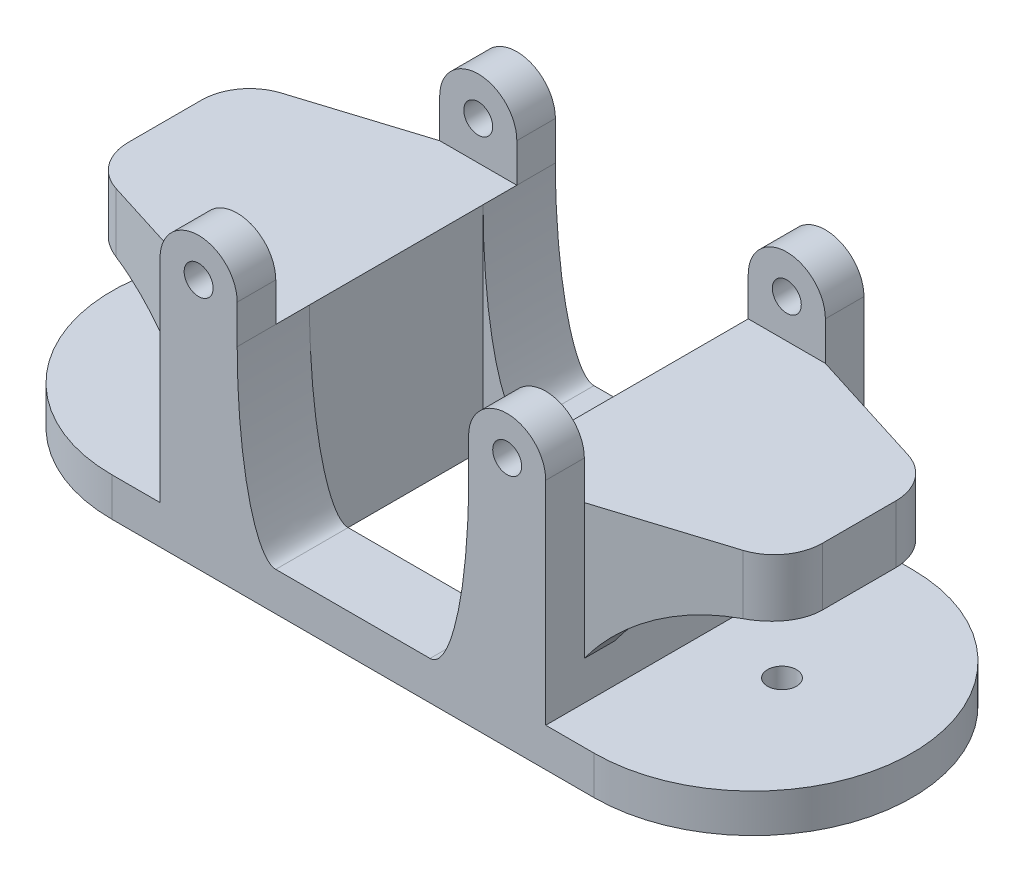
SolidWorks part; units mm, degrees
ref_plane "Front Plane" through (0, 0, 0) normal (0, 0, 1) x (1, 0, 0)
ref_plane "Top Plane" through (0, 0, 0) normal (0, 1, 0) x (1, 0, 0)
ref_plane "Right Plane" through (0, 0, 0) normal (1, 0, 0) x (0, 0, -1)
sketch "Sketch1" plane through (0, 0, 0) normal (0, 1, 0) x (1, 0, 0)
  line L1 (-16, 16.5) -> (16, 16.5)
  line L2 (-16, 16.5) -> (-16, -16.5)
  line L3 (-16, -16.5) -> (16, -16.5)
  line L4 (16, 16.5) -> (16, -16.5)
  line L5 (-16, 16.5) -> (16, -16.5) construction
  line L6 (-16, -16.5) -> (16, 16.5) construction
  point P0 (0, 0)
  dimension "D1" = 33
  dimension "D2" = 32
extrude "Boss-Extrude1" add sketch "Sketch1" along normal blind 18 contours L4 L3 L2 L1
shell "Shell1" thickness 4 removed face at (0, 18, 0)
sketch "Sketch2" plane through (0, 0, 0) normal (0, 0, 1) x (1, 0, 0)
  line L8 (-16, 0) -> (-20, 0)
  line L17 (-20, 0) -> (-20, 22)
  line L19 (-12, 22) -> (-12, 18)
  line L20 (-16, 18) -> (16, 18) construction
  line L21 (-12, 18) -> (-16, 18)
  line L22 (-16, 18) -> (-16, 0)
  line L23 (0, -9.9) -> (0, 9.9) construction
  line L24 (16, 18) -> (16, 0)
  line L25 (12, 18) -> (16, 18)
  line L26 (12, 22) -> (12, 18)
  line L27 (20, 0) -> (20, 22)
  line L28 (16, 0) -> (20, 0)
  arc A2 (-20, 22) -> (-12, 22) centre (-16, 22) cw
  circle A3 centre (-16, 22) radius 1.5
  circle A4 centre (16, 22) radius 1.5
  arc A5 (20, 22) -> (12, 22) centre (16, 22) ccw
  dimension "D2" = 4
  dimension "D3" = 3
  dimension "D1" = 4
extrude "Boss-Extrude2" add sketch "Sketch2" along normal mid plane 33
sketch "Sketch10" plane through (-12, 0, 0) normal (1, 0, 0) x (0, 0, -1)
  line L1 (-12.5, 26) -> (12.5, 26)
  line L2 (-12.5, 26) -> (-12.5, 18)
  line L3 (-12.5, 18) -> (12.5, 18)
  line L4 (12.5, 26) -> (12.5, 18)
  line L5 (16.5, 26) -> (-16.5, 26) construction
  line L6 (-16.5, 0) -> (16.5, 0) construction
  point P4 (0, 18)
  dimension "D1" = 25
  dimension "D2" = 18
extrude "Cut-Extrude5" cut sketch "Sketch10" against normal up to next and the other way up to next
sketch "Sketch11" plane through (0, 18, 0) normal (0, 1, 0) x (1, 0, 0)
  line L0 (-20, 12.5) -> (-32.5, 8.5689)
  line L1 (-36, 3.7992) -> (-36, -3.7992)
  line L2 (-32.5, -8.5689) -> (-20, -12.5)
  line L3 (-12, -12.5) -> (-12, 12.5) construction
  line L4 (0, -9.9) -> (0, 9.9) construction
  line L5 (32.5, -8.5689) -> (20, -12.5)
  line L6 (36, 3.7992) -> (36, -3.7992)
  line L7 (20, 12.5) -> (32.5, 8.5689)
  line L8 (-20, 12.5) -> (-20, -12.5)
  line L9 (20, 12.5) -> (20, -12.5)
  arc A0 (-32.5, 8.5689) -> (-36, 3.7992) centre (-31, 3.7992) ccw
  arc A1 (-36, -3.7992) -> (-32.5, -8.5689) centre (-31, -3.7992) ccw
  arc A2 (36, -3.7992) -> (32.5, -8.5689) centre (31, -3.7992) cw
  arc A3 (32.5, 8.5689) -> (36, 3.7992) centre (31, 3.7992) cw
  dimension "D2" = 5
  dimension "D1" = 24
  dimension "D3" = 12.5
extrude "Boss-Extrude3" add sketch "Sketch11" against normal blind 14
sketch "Sketch12" plane through (0, 4, 0) normal (0, -1, 0) x (1, 0, 0)
  line L12 (-36, -3.7992) -> (-36, 3.7992) construction
  line L13 (-32.5, 8.5689) -> (-20, 12.5) construction
  line L14 (-20, -12.5) -> (-32.5, -8.5689) construction
  line L15 (-20, 12.5) -> (-20, -12.5) construction
  line L16 (-20, -9.3551) -> (-20, 9.3551)
  line L17 (-20, 9.3551) -> (-31.6, 5.7071)
  line L18 (-33, 3.7992) -> (-33, -3.7992)
  line L19 (-31.6, -5.7071) -> (-20, -9.3551)
  line L28 (0, -9.9) -> (0, 9.9) construction
  line L29 (31.6, -5.7071) -> (20, -9.3551)
  line L30 (33, 3.7992) -> (33, -3.7992)
  line L31 (20, 9.3551) -> (31.6, 5.7071)
  line L32 (20, -9.3551) -> (20, 9.3551)
  arc A10 (-31.6, 5.7071) -> (-33, 3.7992) centre (-31, 3.7992) ccw
  arc A11 (-33, -3.7992) -> (-31.6, -5.7071) centre (-31, -3.7992) ccw
  arc A12 (-32.5, 8.5689) -> (-36, 3.7992) centre (-31, 3.7992) ccw construction
  arc A13 (-36, -3.7992) -> (-32.5, -8.5689) centre (-31, -3.7992) ccw construction
  arc A14 (33, -3.7992) -> (31.6, -5.7071) centre (31, -3.7992) cw
  arc A15 (31.6, 5.7071) -> (33, 3.7992) centre (31, 3.7992) cw
  dimension "D1" = 3
extrude "Cut-Extrude6" cut sketch "Sketch12" against normal blind 10
sketch "Sketch13" plane through (0, 0, 16.5) normal (0, 0, 1) x (1, 0, 0)
  line L0 (-36, 4) -> (-36, 18) construction
  line L1 (-32.5, 18) -> (-20, 18) construction
  line L2 (-36, 12) -> (-36, 4)
  line L3 (-36, 4) -> (-20, 4)
  line L4 (0, -9.9) -> (0, 9.9) construction
  line L5 (36, 4) -> (20, 4)
  line L6 (36, 12) -> (36, 4)
  arc A0 (-20, 4) -> (-36, 12) centre (-34.9857, -5.9714) ccw
  arc A1 (20, 4) -> (36, 12) centre (34.9857, -5.9714) cw
  dimension "D2" = 18
  dimension "D1" = 6
extrude "Cut-Extrude7" cut sketch "Sketch13" against normal up to next
sketch "Sketch15" plane through (0, 0, 0) normal (0, -1, 0) x (1, 0, 0)
  line L0 (-25, 16.5) -> (25, 16.5)
  line L1 (25, -16.5) -> (-25, -16.5)
  line L2 (-20, -16.5) -> (20, -16.5) construction
  line L3 (-20, 16.5) -> (20, 16.5) construction
  line L5 (0, -14.3) -> (0, 14.3) construction
  arc A0 (25, 16.5) -> (25, -16.5) centre (25, 0) cw
  arc A1 (-25, -16.5) -> (-25, 16.5) centre (-25, 0) cw
  circle A2 centre (-28, 0) radius 1.5
  circle A3 centre (28, 0) radius 1.5
  point P11 (0, 16.5)
  dimension "D2" = 28
  dimension "D3" = 3
  dimension "D1" = 50
extrude "Boss-Extrude5" add sketch "Sketch15" along normal blind 4
sketch "Sketch9" plane through (0, 4, 0) normal (0, 1, 0) x (1, 0, 0)
  line L0 (-12, -12.5) -> (-12, 12.5) construction
  line L1 (-12, 9) -> (12, 9)
  line L2 (-12, 9) -> (-12, -9)
  line L3 (-12, -9) -> (12, -9)
  line L4 (12, 9) -> (12, -9)
  line L5 (-12, 9) -> (12, -9) construction
  line L6 (-12, -9) -> (12, 9) construction
  point P0 (0, 0)
  dimension "D1" = 18
extrude "Cut-Extrude4" cut sketch "Sketch9" against normal through all
sketch "Sketch16" plane through (0, 0, 16.5) normal (0, 0, 1) x (1, 0, 0)
  line L0 (-20, 0) -> (-25, 0) construction
  line L1 (-12, 18) -> (12, 18)
  line L2 (-12, 18) -> (-12, 0)
  line L3 (-12, 0) -> (12, 0)
  line L4 (12, 18) -> (12, 0)
extrude "Cut-Extrude8" cut sketch "Sketch16" against normal through all
fillet "Fillet1" radius 18 2 edges at (-12, 0, -12.75) (-12, 0, 12.75) second distance 4 first distance on face at (-12, 9.6667, 0)
fillet "Fillet2" radius 4 2 edges at (12, 0, -12.75) (12, 0, 12.75) second distance 18 first distance on face at (2, 0, -13.6875) first distance on face at (-3, 0, 11.8125)
